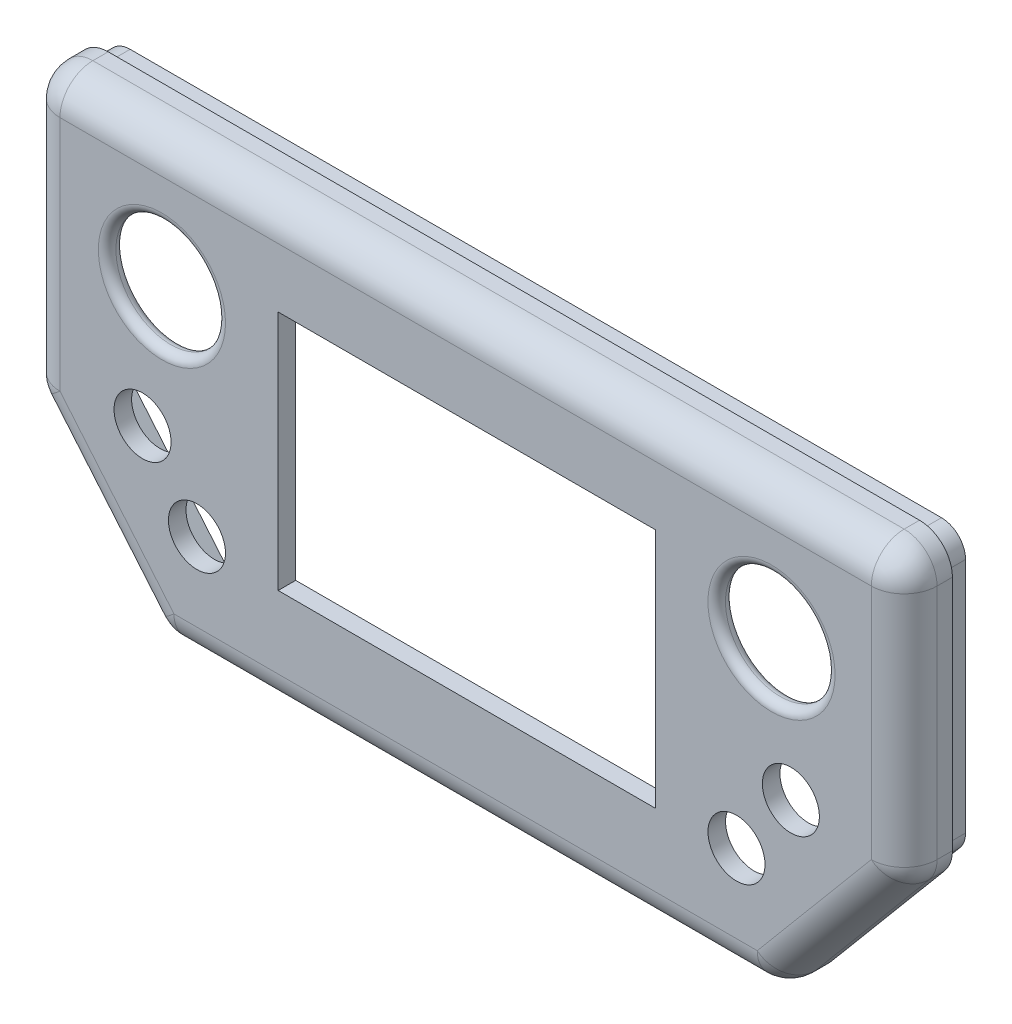
SolidWorks part; units mm, degrees
ref_plane "Front Plane" through (0, 0, 0) normal (0, 0, 1) x (1, 0, 0)
ref_plane "Top Plane" through (0, 0, 0) normal (0, 1, 0) x (1, 0, 0)
ref_plane "Right Plane" through (0, 0, 0) normal (1, 0, 0) x (0, 0, -1)
sketch "Sketch1" plane through (0, 0, 0) normal (0, 0, 1) x (1, 0, 0)
  line L48 (-32.7612, -78.3628) -> (-6.7639, -109.3452)
  line L49 (-34.5159, -19.5243) -> (-34.5159, -73.5419)
  line L50 (157.9841, -12.0243) -> (-27.0159, -12.0243)
  line L51 (165.4841, -73.5419) -> (165.4841, -19.5243)
  line L58 (137.7322, -109.3452) -> (163.7295, -78.3628)
  line L59 (-1.0185, -112.0243) -> (131.9868, -112.0243)
  line L66 (-32.7612, -78.3628) -> (-6.7639, -109.3452)
  line L67 (-34.5159, -19.5243) -> (-34.5159, -73.5419)
  line L68 (157.9841, -12.0243) -> (-27.0159, -12.0243)
  line L69 (165.4841, -73.5419) -> (165.4841, -19.5243)
  line L76 (137.7322, -109.3452) -> (163.7295, -78.3628)
  line L77 (-1.0185, -112.0243) -> (131.9868, -112.0243)
  arc A48 (-6.7639, -109.3452) -> (-1.0185, -112.0243) centre (-1.0185, -104.5243) ccw
  arc A49 (-34.5159, -73.5419) -> (-32.7612, -78.3628) centre (-27.0159, -73.5419) ccw
  arc A50 (-27.0159, -12.0243) -> (-34.5159, -19.5243) centre (-27.0159, -19.5243) ccw
  arc A51 (165.4841, -19.5243) -> (157.9841, -12.0243) centre (157.9841, -19.5243) ccw
  arc A52 (163.7295, -78.3628) -> (165.4841, -73.5419) centre (157.9841, -73.5419) ccw
  arc A53 (131.9868, -112.0243) -> (137.7322, -109.3452) centre (131.9868, -104.5243) ccw
  arc A60 (-6.7639, -109.3452) -> (-1.0185, -112.0243) centre (-1.0185, -104.5243) ccw
  arc A61 (-34.5159, -73.5419) -> (-32.7612, -78.3628) centre (-27.0159, -73.5419) ccw
  arc A68 (-27.0159, -12.0243) -> (-34.5159, -19.5243) centre (-27.0159, -19.5243) ccw
  arc A69 (165.4841, -19.5243) -> (157.9841, -12.0243) centre (157.9841, -19.5243) ccw
  arc A70 (163.7295, -78.3628) -> (165.4841, -73.5419) centre (157.9841, -73.5419) ccw
  arc A71 (131.9868, -112.0243) -> (137.7322, -109.3452) centre (131.9868, -104.5243) ccw
  dimension "D1" = 0
extrude "Boss-Extrude1" add sketch "Sketch1" along normal blind 11
shell "Shell1" thickness 4 removed face at (65.4841, -67.3435, 0)
fillet "Fillet1" radius 7.5 12 edges at (65.4841, -112.0243, 11) (-19.7625, -93.854, 11) (-34.0636, -76.1071, 11) (-34.5159, -46.5331, 11) (-32.3192, -14.221, 11) (65.4841, -12.0243, 11) (163.2874, -14.221, 11) (165.4841, -46.5331, 11) (165.0318, -76.1071, 11) (150.7308, -93.854, 11) (135.1565, -111.3216, 11) (-4.1882, -111.3216, 11)
sketch "Sketch2" plane through (0, 0, 0) normal (0, 0, -1) x (-1, 0, 0)
  line L6 (5.2318, -108.0597) -> (31.2291, -77.0773)
  line L15 (5.2318, -108.0597) -> (31.2291, -77.0773)
  line L25 (32.5159, -73.5419) -> (32.5159, -19.5243)
  line L26 (-131.9868, -110.0243) -> (1.0185, -110.0243)
  line L32 (-131.9868, -110.0243) -> (1.0185, -110.0243)
  line L35 (32.5159, -73.5419) -> (32.5159, -19.5243)
  line L37 (27.0159, -14.0243) -> (-157.9841, -14.0243)
  line L39 (3.6997, -106.7741) -> (29.697, -75.7917)
  line L41 (3.6997, -106.7741) -> (29.697, -75.7917)
  line L47 (-131.9868, -108.0243) -> (1.0185, -108.0243)
  line L53 (-131.9868, -108.0243) -> (1.0185, -108.0243)
  line L54 (30.5159, -73.5419) -> (30.5159, -19.5243)
  line L60 (27.0159, -14.0243) -> (-157.9841, -14.0243)
  line L61 (-163.4841, -19.5243) -> (-163.4841, -73.5419)
  line L62 (-163.4841, -19.5243) -> (-163.4841, -73.5419)
  line L63 (-162.1974, -77.0773) -> (-136.2001, -108.0597)
  line L64 (-162.1974, -77.0773) -> (-136.2001, -108.0597)
  line L65 (30.5159, -73.5419) -> (30.5159, -19.5243)
  line L66 (27.0159, -16.0243) -> (-157.9841, -16.0243)
  line L67 (27.0159, -16.0243) -> (-157.9841, -16.0243)
  line L68 (-161.4841, -19.5243) -> (-161.4841, -73.5419)
  line L69 (-161.4841, -19.5243) -> (-161.4841, -73.5419)
  line L70 (-160.6653, -75.7917) -> (-134.668, -106.7741)
  line L71 (-160.6653, -75.7917) -> (-134.668, -106.7741)
  arc A12 (1.0185, -110.0243) -> (5.2318, -108.0597) centre (1.0185, -104.5243) ccw
  arc A16 (1.0185, -110.0243) -> (5.2318, -108.0597) centre (1.0185, -104.5243) ccw
  arc A25 (31.2291, -77.0773) -> (32.5159, -73.5419) centre (27.0159, -73.5419) ccw
  arc A34 (31.2291, -77.0773) -> (32.5159, -73.5419) centre (27.0159, -73.5419) ccw
  arc A43 (32.5159, -19.5243) -> (27.0159, -14.0243) centre (27.0159, -19.5243) ccw
  arc A45 (32.5159, -19.5243) -> (27.0159, -14.0243) centre (27.0159, -19.5243) ccw
  arc A47 (1.0185, -108.0243) -> (3.6997, -106.7741) centre (1.0185, -104.5243) ccw
  arc A61 (1.0185, -108.0243) -> (3.6997, -106.7741) centre (1.0185, -104.5243) ccw
  arc A63 (29.697, -75.7917) -> (30.5159, -73.5419) centre (27.0159, -73.5419) ccw
  arc A65 (29.697, -75.7917) -> (30.5159, -73.5419) centre (27.0159, -73.5419) ccw
  arc A67 (30.5159, -19.5243) -> (27.0159, -16.0243) centre (27.0159, -19.5243) ccw
  arc A69 (30.5159, -19.5243) -> (27.0159, -16.0243) centre (27.0159, -19.5243) ccw
  arc A71 (-157.9841, -14.0243) -> (-163.4841, -19.5243) centre (-157.9841, -19.5243) ccw
  arc A72 (-157.9841, -14.0243) -> (-163.4841, -19.5243) centre (-157.9841, -19.5243) ccw
  arc A73 (-163.4841, -73.5419) -> (-162.1974, -77.0773) centre (-157.9841, -73.5419) ccw
  arc A74 (-163.4841, -73.5419) -> (-162.1974, -77.0773) centre (-157.9841, -73.5419) ccw
  arc A75 (-136.2001, -108.0597) -> (-131.9868, -110.0243) centre (-131.9868, -104.5243) ccw
  arc A76 (-136.2001, -108.0597) -> (-131.9868, -110.0243) centre (-131.9868, -104.5243) ccw
  arc A77 (-157.9841, -16.0243) -> (-161.4841, -19.5243) centre (-157.9841, -19.5243) ccw
  arc A78 (-157.9841, -16.0243) -> (-161.4841, -19.5243) centre (-157.9841, -19.5243) ccw
  arc A79 (-161.4841, -73.5419) -> (-160.6653, -75.7917) centre (-157.9841, -73.5419) ccw
  arc A80 (-161.4841, -73.5419) -> (-160.6653, -75.7917) centre (-157.9841, -73.5419) ccw
  arc A81 (-134.668, -106.7741) -> (-131.9868, -108.0243) centre (-131.9868, -104.5243) ccw
  arc A82 (-134.668, -106.7741) -> (-131.9868, -108.0243) centre (-131.9868, -104.5243) ccw
  dimension "D1" = 2
  dimension "D2" = 4
extrude "Boss-Extrude2" add sketch "Sketch2" along normal blind 5
sketch "Sketch3" plane through (0, 0, 11) normal (0, 0, 1) x (1, 0, 0)
  line L1 (22.7341, -33.0243) -> (108.7341, -33.0243)
  line L2 (22.7341, -33.0243) -> (22.7341, -88.0243)
  line L3 (22.7341, -88.0243) -> (108.7341, -88.0243)
  line L4 (108.7341, -33.0243) -> (108.7341, -88.0243)
  line L5 (-1.0185, -104.5243) -> (131.9868, -104.5243) construction
  dimension "D1" = 86
  dimension "D2" = 55
  dimension "D3" = 16.5
extrude "Cut-Extrude1" cut sketch "Sketch3" against normal blind 10
sketch "Sketch4" plane through (0, 0, 11) normal (0, 0, 1) x (1, 0, 0)
  line L0 (65.7341, -15.7243) -> (65.7341, -105.7243) construction
  line L1 (-27.0159, -73.5419) -> (-1.0185, -104.5243) construction
  circle A0 centre (-3.7659, -41.2243) radius 12.5
  circle A2 centre (-8.1836, -70.9616) radius 6.5
  circle A3 centre (4.2185, -86.6519) radius 6.5
  circle A4 centre (127.2497, -86.6519) radius 6.5
  circle A5 centre (139.6519, -70.9616) radius 6.5
  circle A6 centre (135.2341, -41.2243) radius 12.5
  dimension "D1" = 25
  dimension "D2" = 13
  dimension "D7" = 20
  dimension "D3" = 15.5
extrude "Cut-Extrude2" cut sketch "Sketch4" against normal blind 10
fillet "Fillet2" radius 2 4 edges at (8.7341, -41.2243, 7) (8.7341, -41.2243, 11) (147.7341, -41.2243, 7) (122.7341, -41.2243, 11)
